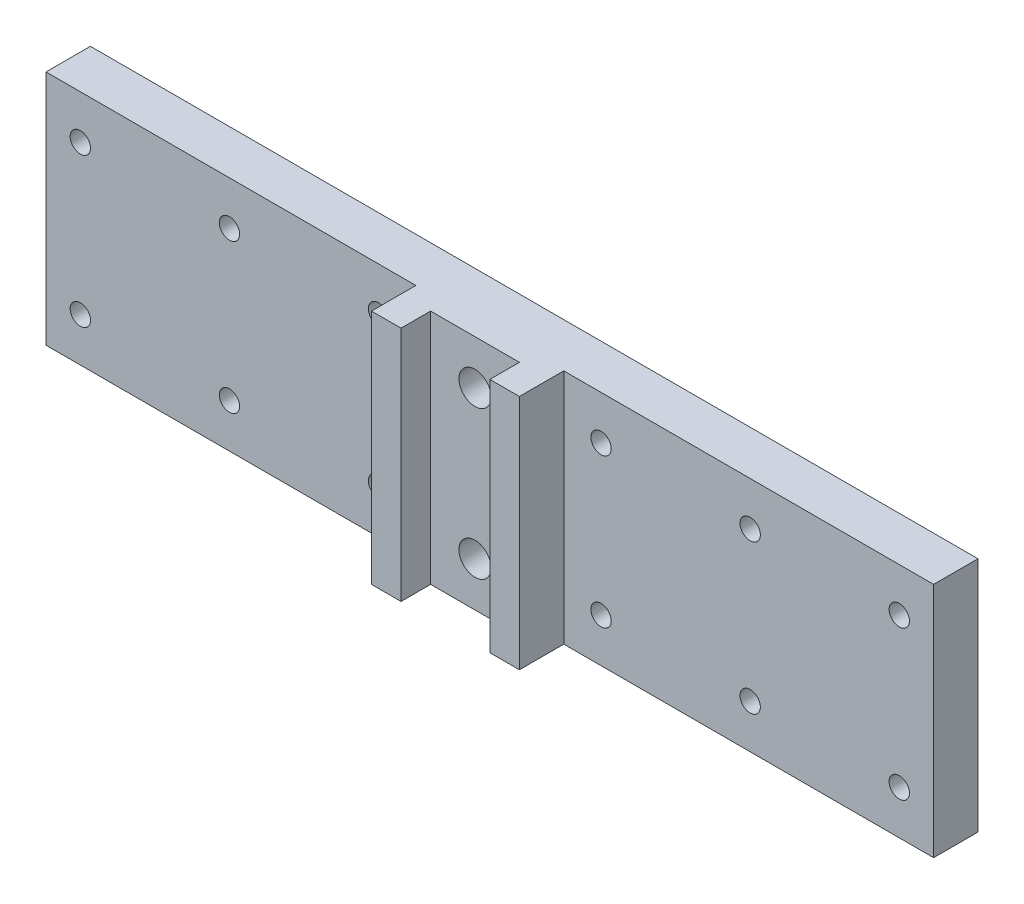
SolidWorks part; units mm, degrees
ref_plane "Front Plane" through (0, 0, 0) normal (0, 0, 1) x (1, 0, 0)
ref_plane "Top Plane" through (0, 0, 0) normal (0, 1, 0) x (1, 0, 0)
ref_plane "Right Plane" through (0, 0, 0) normal (1, 0, 0) x (0, 0, -1)
sketch "Sketch1" plane through (0, 0, 0) normal (0, 0, 1) x (1, 0, 0)
  line L1 (0, 0) -> (95.25, 0)
  line L2 (0, 0) -> (0, 25.4)
  line L3 (0, 25.4) -> (95.25, 25.4)
  line L4 (95.25, 0) -> (95.25, 25.4)
  dimension "D1" = 25.4
  dimension "D2" = 95.25
extrude "Boss-Extrude1" add sketch "Sketch1" along normal blind 9.525
sketch "Sketch2" plane through (0, 25.4, 0) normal (0, 1, 0) x (1, 0, 0)
  line L0 (47.625, 0) -> (47.625, -9.525) construction
  line L1 (95.25, 0) -> (0, 0) construction
  line L2 (95.25, -9.525) -> (0, -9.525) construction
  line L3 (52.3875, -9.525) -> (52.3875, -6.35)
  line L4 (0, -9.525) -> (39.6875, -9.525)
  line L5 (0, -9.525) -> (0, -4.7625)
  line L6 (0, -4.7625) -> (39.6875, -4.7625)
  line L7 (39.6875, -9.525) -> (39.6875, -4.7625)
  line L8 (52.3875, -9.525) -> (42.8625, -9.525)
  line L10 (52.3875, -6.35) -> (42.8625, -6.35)
  line L11 (42.8625, -9.525) -> (42.8625, -6.35)
  line L12 (55.5625, -9.525) -> (55.5625, -4.7625)
  line L13 (95.25, -4.7625) -> (55.5625, -4.7625)
  line L14 (95.25, -9.525) -> (95.25, -4.7625)
  line L15 (95.25, -9.525) -> (55.5625, -9.525)
  dimension "D1" = 4.7625
  dimension "D2" = 6.35
  dimension "D3" = 9.525
  dimension "D4" = 3.175
extrude "Cut-Extrude1" cut sketch "Sketch2" against normal through all
hole_wizard "#8-32 Tapped Hole1" positions "Sketch7" profile "Sketch8" tap size "#8-32" standard "ANSI Inch" end condition through all
sketch "Sketch7" plane through (0, 0, 6.35) normal (0, 0, 1) x (1, 0, 0)
  line L0 (52.3875, 12.7) -> (42.8625, 12.7) construction
  line L1 (52.3875, 0) -> (52.3875, 25.4) construction
  line L2 (42.8625, 0) -> (42.8625, 25.4) construction
  line L4 (47.625, 25.4) -> (47.625, 0) construction
  line L5 (52.3875, 25.4) -> (42.8625, 25.4) construction
  line L6 (52.3875, 0) -> (42.8625, 0) construction
  point P16 (47.625, 4.7625)
  point P19 (47.625, 20.6375)
  dimension "D1" = 7.9375
sketch "Sketch8" plane through (47.625, 4.7625, 6.35) normal (1, 0, 0) x (0, -1, 0)
  line L0 (0, 0) -> (0, 6.35)
  line L1 (0, 6.35) -> (1.7272, 6.35)
  line L2 (1.7272, 6.35) -> (1.7272, 0)
  line L5 (1.7272, 0) -> (0, 0)
  line L11 (0, -6.35) -> (0, 107.95) construction
  dimension "Thread Major Dia." = 3.4544
  dimension "Thru Tap Drill Depth" = 6.35
hole_wizard "#44 (0.086) Diameter Hole1" positions "Sketch14" profile "Sketch13" hole size "#44" standard "ANSI Inch"
sketch "Sketch14" plane through (0, 0, 0) normal (0, 0, -1) x (-1, 0, 0)
  line L0 (-47.625, 25.4) -> (-47.625, 0) construction
  line L1 (-95.25, 25.4) -> (0, 25.4) construction
  line L2 (0, 0) -> (-95.25, 0) construction
  line L4 (-47.625, 12.7) -> (0, 12.7) construction
  line L5 (0, 25.4) -> (0, 0) construction
  line L9 (-35.685, 20.7) -> (-3.685, 20.7) construction
  line L11 (-19.685, 20.7) -> (-19.685, 12.7) construction
  line L12 (-35.685, 4.7) -> (-3.685, 4.7) construction
  line L13 (-59.565, 4.7) -> (-91.565, 4.7) construction
  line L14 (-59.565, 20.7) -> (-91.565, 20.7) construction
  point P19 (-35.685, 20.7)
  point P20 (-3.685, 20.7)
  point P23 (-19.685, 20.7)
  point P28 (-35.685, 4.7)
  point P29 (-3.685, 4.7)
  point P30 (-59.565, 4.7)
  point P31 (-91.565, 4.7)
  point P32 (-59.565, 20.7)
  point P33 (-91.565, 20.7)
  point P34 (-75.565, 20.7)
  point P36 (-75.565, 4.7)
  point P38 (-19.685, 4.7)
  dimension "D1" = 32
  dimension "D2" = 8
  dimension "D3" = 27.94
sketch "Sketch13" plane through (35.685, 20.7, 0) normal (1, 0, 0) x (0, 1, 0)
  line L0 (0, 0) -> (0, 10.3083)
  line L1 (0, 10.3083) -> (1.0922, 9.652)
  line L2 (1.0922, 9.652) -> (1.0922, 0)
  line L5 (1.0922, 0) -> (0, 0)
  line L10 (0, 10.3083) -> (-1.0922, 9.652) construction
  line L11 (0, -6.35) -> (0, 107.95) construction
  dimension "Hole Dia." = 2.1844
  dimension "Hole Depth" = 9.652
  dimension "Drill Angle" = 118
